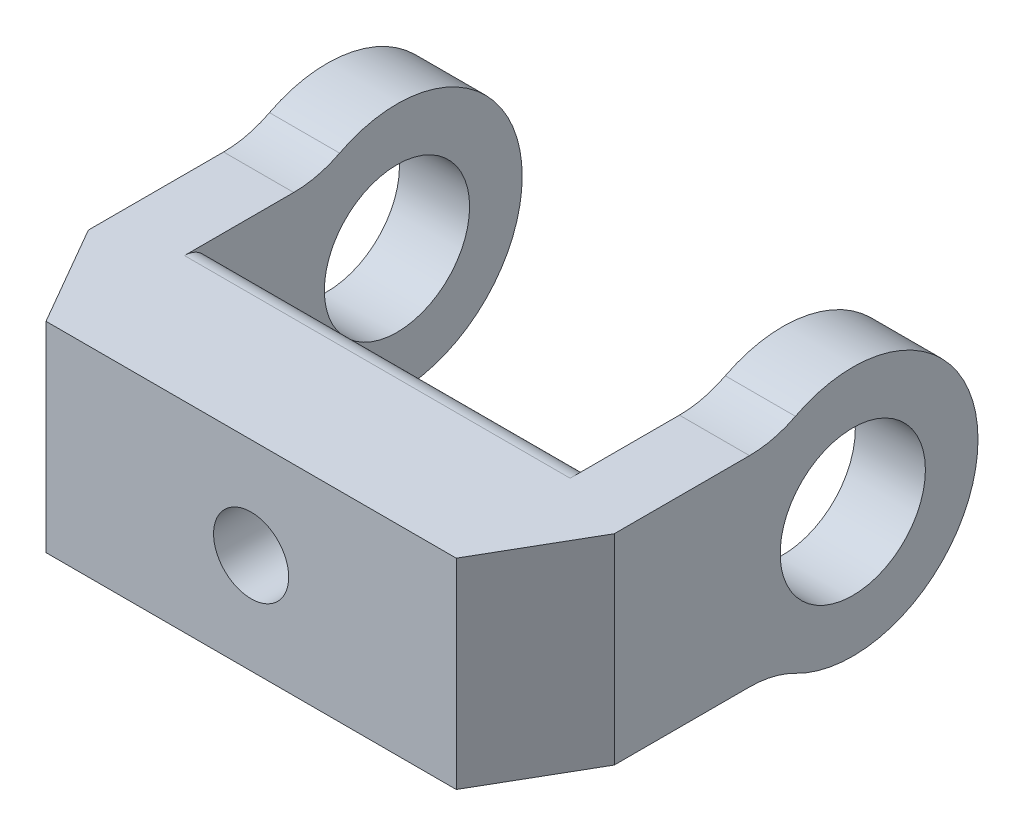
SolidWorks part; units mm, degrees
ref_plane "Front Plane" through (0, 0, 0) normal (0, 0, 1) x (1, 0, 0)
ref_plane "Top Plane" through (0, 0, 0) normal (0, 1, 0) x (1, 0, 0)
ref_plane "Right Plane" through (0, 0, 0) normal (1, 0, 0) x (0, 0, -1)
sketch "Sketch1" plane through (0, 0, 0) normal (0, 1, 0) x (1, 0, 0)
  line L1 (-10.5, -2.2617) -> (10.5, -2.2617)
  line L2 (-10.5, -2.2617) -> (-10.5, 2.2617)
  line L3 (-10.5, 2.2617) -> (10.5, 2.2617)
  line L4 (10.5, -2.2617) -> (10.5, 2.2617)
  line L5 (-10.5, -2.2617) -> (10.5, 2.2617) construction
  line L6 (-10.5, 2.2617) -> (10.5, -2.2617) construction
  point P0 (0, 0)
  dimension "D1" = 21
extrude "Boss-Extrude1" add sketch "Sketch1" along normal blind 8
sketch "Sketch2" plane through (0, 0, -2.2617) normal (0, 0, -1) x (-1, 0, 0)
  line L0 (-10.5, 0) -> (10.5, 0) construction
  line L1 (10.5, 8) -> (7.7, 8)
  line L2 (10.5, 8) -> (10.5, 0)
  line L3 (10.5, 0) -> (7.7, 0)
  line L4 (7.7, 8) -> (7.7, 0)
  line L5 (0, 0) -> (0, -1.4775) construction
  line L6 (-7.7, 8) -> (-7.7, 0)
  line L7 (-10.5, 0) -> (-7.7, 0)
  line L8 (-10.5, 8) -> (-10.5, 0)
  line L9 (-10.5, 8) -> (-7.7, 8)
  dimension "D1" = 15.4
extrude "Boss-Extrude2" add sketch "Sketch2" along normal blind 10
sketch "Sketch3" plane through (10.5, 0, 0) normal (1, 0, 0) x (0, 0, -1)
  line L0 (12.2617, 4) -> (8.2617, 4) construction
  line L1 (12.2617, 8) -> (12.2617, 0) construction
  circle A0 centre (8.2617, 4) radius 2.9
  dimension "D1" = 5.8
  dimension "D2" = 4
extrude "Cut-Extrude1" cut sketch "Sketch3" against normal blind 34
fillet "Fillet1" radius 4 4 edges at (9.1, 0, -12.2617) (-9.1, 0, -12.2617) (-9.1, 8, -12.2617) (9.1, 8, -12.2617)
sketch "Sketch4" plane through (7.7, 0, 0) normal (-1, 0, 0) x (0, 0, 1)
  circle A0 centre (-8.2617, 4) radius 8
  dimension "D1" = 16
extrude "Cut-Extrude2" cut sketch "Sketch4" along normal up to surface (15.4 mm away) up to face at (-7.7, 4, -5.3617)
fillet "Fillet2" radius 1 2 edges at (0, 0, -1.3335) (0, 8, -1.3335)
sketch "Sketch6" plane through (0, 0, 2.2617) normal (0, 0, 1) x (1, 0, 0)
  line L4 (-10.5, 0) -> (10.5, 0)
  line L5 (10.5, 0) -> (10.5, 8)
  line L6 (10.5, 8) -> (-10.5, 8)
  line L7 (-10.5, 8) -> (-10.5, 0)
  line L8 (-10.5, 0) -> (10.5, 0)
  line L9 (10.5, 0) -> (10.5, 8)
  line L10 (10.5, 8) -> (-10.5, 8)
  line L11 (-10.5, 8) -> (-10.5, 0)
  dimension "D1" = 0
extrude "Boss-Extrude3" add sketch "Sketch6" along normal blind 3
sketch "Sketch7" plane through (0, 0, 5.2617) normal (0, 0, 1) x (1, 0, 0)
  line L0 (0, 0) -> (0, 8) construction
  line L1 (10.5, 8) -> (-10.5, 8) construction
  circle A0 centre (0, 4) radius 1.5
  dimension "D1" = 3
extrude "Cut-Extrude3" cut sketch "Sketch7" against normal blind 12
sketch "Sketch8" plane through (0, 0, 0) normal (0, 0, 1) x (1, 0, 0)
  circle A0 centre (0, 4) radius 3
  dimension "D1" = 6
extrude "Cut-Extrude4" cut sketch "Sketch8" against normal blind 12 and the other way blind 2.8
sketch "Sketch9" plane through (0, 0, 2.8) normal (0, 0, -1) x (-1, 0, 0)
  circle A0 centre (0, 4) radius 2.75
  dimension "D1" = 5.5
extrude "Boss-Extrude4" add sketch "Sketch9" along normal blind 3 separate body
chamfer "Chamfer1" distance 4 angle 30 2 edges at (10.5, 4, 5.2617) (-10.5, 4, 5.2617) first distance on face at (10.5, 4, -11.1617) first distance on face at (-10.5, 4, -11.1617)
sketch "Sketch10" plane through (10.5, 0, 0) normal (1, 0, 0) x (0, 0, -1)
  circle A0 centre (8.2617, 4) radius 2.9 construction
  circle A1 centre (8.2617, 4) radius 2.9
  circle A2 centre (8.2617, 4) radius 5
  dimension "D1" = 10
extrude "Boss-Extrude5" add sketch "Sketch10" against normal up to surface (2.8 mm away) up to face at (7.7, 6.9, -8.2617)
sketch "Sketch11" plane through (-10.5, 0, 0) normal (-1, 0, 0) x (0, 0, 1)
  circle A1 centre (-8.2617, 4) radius 5
  circle A2 centre (-8.2617, 4) radius 5
  circle A3 centre (-8.2617, 4) radius 2.9
  circle A4 centre (-8.2617, 4) radius 2.9
  dimension "D1" = 0
  dimension "D2" = 0
extrude "Boss-Extrude6" add sketch "Sketch11" against normal up to surface (2.8 mm away) up to face at (-7.7, 4, -5.3617)
fillet "Fillet3" radius 4 4 edges at (-9.1, 0, -5.2617) (9.1, 0, -5.2617) (-9.1, 8, -5.2617) (9.1, 8, -5.2617)
